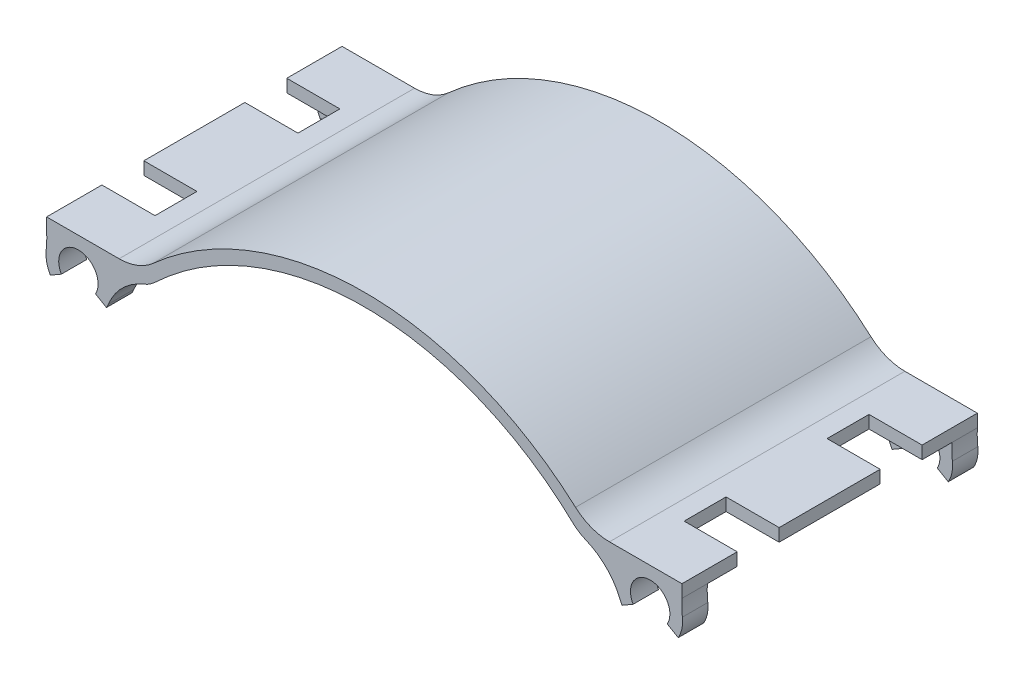
SolidWorks part; units mm, degrees
ref_plane "Front Plane" through (0, 0, 0) normal (0, 0, 1) x (1, 0, 0)
ref_plane "Top Plane" through (0, 0, 0) normal (0, 1, 0) x (1, 0, 0)
ref_plane "Right Plane" through (0, 0, 0) normal (1, 0, 0) x (0, 0, -1)
sketch "Sketch3" plane through (0, 0, 0) normal (0, 0, 1) x (1, 0, 0)
  line L0 (-116.5461, -10.4455) -> (-26.5461, -10.4455) construction
  line L1 (-71.5461, -10.4455) -> (-71.5461, 21.0096) construction
  circle A0 centre (-116.5461, -10.4455) radius 3.1
  circle A1 centre (-26.5461, -10.4455) radius 3.1 construction
  circle A2 centre (-116.5461, -10.4455) radius 5.1
  circle A3 centre (-26.5461, -10.4455) radius 3.1
  circle A4 centre (-26.5461, -10.4455) radius 5.1
  dimension "D1" = 6.2
  dimension "D2" = 2
extrude "Boss-Extrude2" add sketch "Sketch3" along normal blind 4 separate body
sketch "Sketch4" plane through (0, 0, 4) normal (0, 0, 1) x (1, 0, 0)
  line L0 (-116.5461, -10.4455) -> (-116.5461, -20.6145) construction
  line L1 (-116.5461, -10.4455) -> (-134.1595, -20.6145)
  line L2 (-134.1595, -20.6145) -> (-98.9328, -20.6145)
  line L3 (-98.9328, -20.6145) -> (-116.5461, -10.4455)
  line L4 (-116.5461, -10.4455) -> (-26.5461, -10.4455) construction
  line L5 (-26.5461, -10.4455) -> (-8.9328, -20.6145)
  line L6 (-8.9328, -20.6145) -> (-44.1595, -20.6145)
  line L7 (-71.5461, -10.4455) -> (-71.5461, 19.9827) construction
  line L8 (-44.1595, -20.6145) -> (-26.5461, -10.4455)
  point P3 (-116.5461, -20.6145)
  dimension "D1" = 120
extrude "Cut-Extrude1" cut sketch "Sketch4" against normal up to surface (4 mm away) up to face at (-111.4461, -10.4455, 0)
ref_plane "Plane2" through (0, 0, 23.25) normal (0, 0, 1) x (1, 0, 0)
mirror "Mirror2" about plane through (0, 0, 23.25) normal (0, 0, 1) of bodies 103 106
ref_plane "Plane3" through (0, 0, 23.25) normal (0, 0, 1) x (1, 0, 0)
sketch "Sketch6" plane through (0, 0, 23.25) normal (0, 0, 1) x (1, 0, 0)
  line L0 (-121.5461, -7.3455) -> (-106.1006, -7.3455)
  line L1 (-121.5461, -7.3455) -> (-121.5461, -5.3455)
  line L2 (-121.5461, -5.3455) -> (-106.944, -5.3455)
  line L4 (-71.5461, 9.4045) -> (-71.5461, 22.7158) construction
  line L5 (-21.5461, -7.3455) -> (-21.5461, -5.3455)
  line L6 (-21.5461, -7.3455) -> (-36.9916, -7.3455)
  line L7 (-21.5461, -5.3455) -> (-36.1482, -5.3455)
  line L8 (-122.0461, -78.4455) -> (-122.0461, -2.4455) construction
  circle A0 centre (-71.5461, -40.4455) radius 45.85 construction
  circle A1 centre (-71.5461, -40.4455) radius 45.85 construction
  arc A2 (-36.9916, -7.3455) -> (-106.1006, -7.3455) centre (-71.5461, -40.4455) ccw
  arc A3 (-36.1482, -5.3455) -> (-106.944, -5.3455) centre (-71.5461, -40.4455) ccw
  arc A5 (-113.8614, -11.9955) -> (-119.2308, -11.9955) centre (-116.5461, -10.4455) ccw construction
  arc A6 (-113.8614, -11.9955) -> (-119.2308, -11.9955) centre (-116.5461, -10.4455) ccw construction
  circle A7 centre (-71.5461, -40.4455) radius 49.85 construction
  circle A8 centre (-71.5461, -40.4455) radius 47.85 construction
  dimension "D3" = 2
  dimension "D4" = 0.5
  dimension "D1" = 2
  dimension "D2" = 2
extrude "Boss-Extrude3" add sketch "Sketch6" along normal up to surface and the other way up to surface
sketch "Sketch7" plane through (0, -5.3455, 0) normal (0, 1, 0) x (1, 0, 0)
  line L0 (-113.1877, -15.3) -> (-113.1877, -8.7)
  line L1 (-113.1877, -8.7) -> (-122.8461, -8.7)
  line L2 (-122.8461, -8.7) -> (-122.8461, -15.3)
  line L3 (-122.8461, -15.3) -> (-113.1877, -15.3)
  line L4 (-122.0461, -14.5) -> (-113.9877, -14.5)
  line L5 (-113.9877, -14.5) -> (-113.9877, -9.5)
  line L6 (-113.9877, -9.5) -> (-122.0461, -9.5)
  line L7 (-122.0461, -9.5) -> (-122.0461, -14.5)
  line L8 (-122.0461, -14.5) -> (-113.9877, -14.5) construction
  line L9 (-113.9877, -14.5) -> (-113.9877, -9.5) construction
  line L10 (-113.9877, -9.5) -> (-122.0461, -9.5) construction
  line L11 (-122.0461, -9.5) -> (-122.0461, -14.5) construction
  line L12 (-113.9877, -37) -> (-113.9877, -32)
  line L13 (-113.9877, -32) -> (-122.0461, -32)
  line L14 (-122.0461, -32) -> (-122.0461, -37)
  line L15 (-122.0461, -37) -> (-113.9877, -37)
  line L16 (-113.9877, -37) -> (-113.9877, -32) construction
  line L17 (-113.9877, -32) -> (-122.0461, -32) construction
  line L18 (-122.0461, -32) -> (-122.0461, -37) construction
  line L19 (-122.0461, -37) -> (-113.9877, -37) construction
  line L20 (-113.1877, -37.8) -> (-113.1877, -31.2)
  line L21 (-113.1877, -31.2) -> (-122.8461, -31.2)
  line L22 (-122.8461, -31.2) -> (-122.8461, -37.8)
  line L23 (-122.8461, -37.8) -> (-113.1877, -37.8)
  line L24 (-71.5461, 0) -> (-71.5461, 38.4252) construction
  line L25 (-36.1482, 0) -> (-106.944, 0) construction
  line L26 (-20.2461, -37.8) -> (-29.9045, -37.8)
  line L27 (-20.2461, -31.2) -> (-20.2461, -37.8)
  line L28 (-29.9045, -31.2) -> (-20.2461, -31.2)
  line L29 (-29.9045, -37.8) -> (-29.9045, -31.2)
  line L30 (-20.2461, -15.3) -> (-29.9045, -15.3)
  line L31 (-20.2461, -8.7) -> (-20.2461, -15.3)
  line L32 (-29.9045, -8.7) -> (-20.2461, -8.7)
  line L33 (-29.9045, -15.3) -> (-29.9045, -8.7)
  dimension "D1" = 0
  dimension "D2" = 0
  dimension "D3" = 0.8
extrude "Cut-Extrude2" cut sketch "Sketch7" against normal up to surface (2 mm away) up to face at (-27.324, -7.3455, 23.25)
fillet "Fillet1" radius 8 2 edges at (-106.944, -5.3455, 23.25) (-36.1482, -5.3455, 23.25)
fillet "Fillet2" radius 6 2 edges at (-36.9916, -7.3455, 23.25) (-106.1006, -7.3455, 23.25)
fillet "Fillet3" radius 10 4 edges at (-112.4964, -7.3455, 2) (-112.4964, -7.3455, 44.5) (-30.5958, -7.3455, 44.5) (-30.5958, -7.3455, 2)
fillet "Fillet4" radius 15 4 edges at (-120.5958, -7.3455, 2) (-120.5958, -7.3455, 44.5) (-22.4964, -7.3455, 44.5) (-22.4964, -7.3455, 2)
